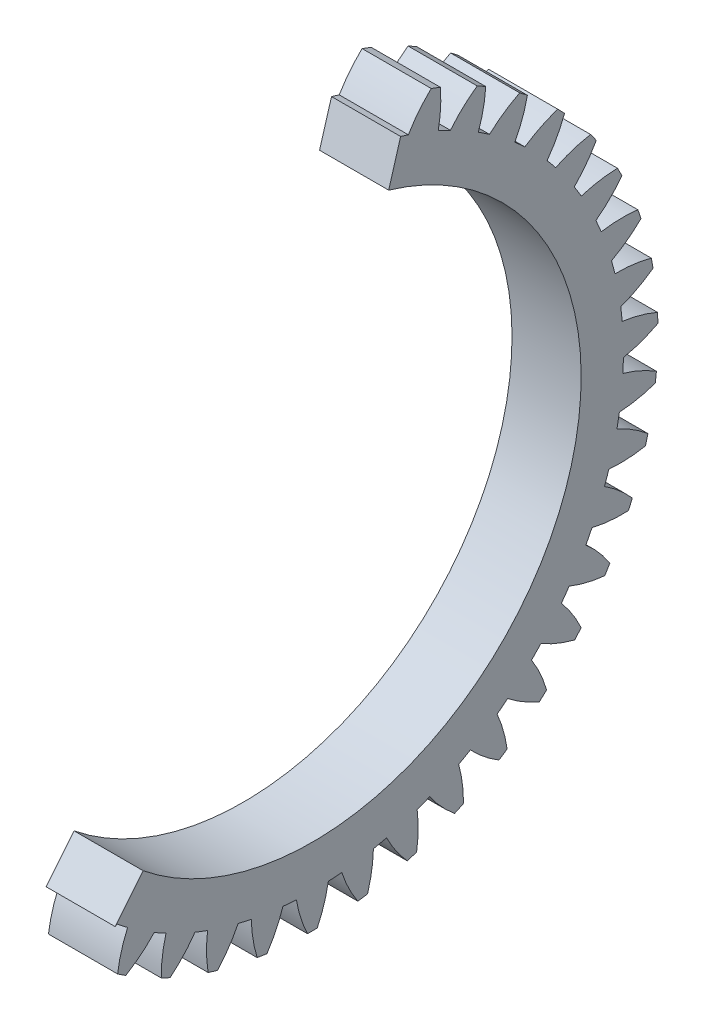
SolidWorks part; units mm, degrees
ref_plane "Plane1" through (0, 0, 0) normal (0, 0, 1) x (1, 0, 0)
ref_plane "Plane2" through (0, 0, 0) normal (0, 1, 0) x (1, 0, 0)
ref_plane "Plane3" through (0, 0, 0) normal (1, 0, 0) x (0, 0, -1)
sketch "HoldingSke" plane through (0, 0, 0) normal (0, 1, 0) x (1, 0, 0)
  line L0 (0, 0) -> (0.3657, -0.341)
  line L1 (-15, 0) -> (100, 0) construction
  line L2 (0, 0) -> (-2.1039, 2.3779)
  line L3 (0, 0) -> (-11.863, 4.5341)
  line L4 (0, 0) -> (6.316, 5.8897)
  line L5 (0, 0) -> (-46.8476, -17.4728)
  line L6 (0, 0) -> (-7.4607, -5.0337)
  line L7 (-2.1039, 2.3779) -> (8.6586, 51.2059)
  line L8 (-76.2, 54.61) -> (-75.2, 54.61)
  line L9 (-71.009, 38.7566) -> (-53.1078, 45.2721)
  line L10 (-76.2, 71.12) -> (104.1128, 71.12)
  line L11 (0, 0) -> (-9, 0)
  line L12 (-76.2, 101.6) -> (-76.133, 101.6)
  line L13 (24.9733, 27.94) -> (52.9518, 28.4284)
  line L14 (24.9733, 27.94) -> (24.9743, 27.94)
  line L15 (24.9733, 27.94) -> (100.4006, 29.5858)
  line L16 (-63.627, -2) -> (-12.827, -2)
  circle A0 centre (0, 0) radius 3
  circle A1 centre (0, 0) radius 37.5
  circle A2 centre (0, 0) radius 37.5
  circle A3 centre (0, 0) radius 3
  dimension "Num_teeth" = 43
  dimension "Pitch_radius" = 180.3128
  dimension "Width" = 9
  dimension "Thickness" = 9
sketch "BasProSke" plane through (0, 0, 0) normal (0, 1, 0) x (1, 0, 0)
  line L0 (-10, 0) -> (60, 0) construction
  line L1 (0, 0) -> (0, 45)
  line L2 (0, 0) -> (9, 0)
  line L3 (9, 0) -> (9, 45)
  line L4 (9, 45) -> (0, 45)
  dimension "Thickness" = 9
  dimension "Diameter" = 90
revolve "Base-Revolve" add sketch "BasProSke" angle 360 about L0
sketch "TooCutSke" plane through (0, 0, 0) normal (1, 0, 0) x (0, 0, -1)
  line L1 (0, 0) -> (0, 107) construction
  line L2 (0, 0) -> (-1.6877, 42.9669) construction
  line L3 (0, 0) -> (-6.274, 85.7216) construction
  line L4 (-1.6877, 42.9669) -> (-3.137, 42.8608) construction
  arc A0 (0.8751, 40.4895) -> (-0.8751, 40.4895) centre (0, 0) ccw
  arc A1 (2.6611, 44.9467) -> (-2.6611, 44.9467) centre (0, 0) ccw
  circle A2 centre (0, 0) radius 43 construction
  circle A3 centre (0, 0) radius 40.4068 construction
  arc A4 (-0.8751, 40.4895) -> (-2.6611, 44.9467) centre (-17.5777, 36.3831) ccw
  arc A5 (2.6611, 44.9467) -> (0.8751, 40.4895) centre (17.5777, 36.3831) ccw
extrude "ToothCut" cut sketch "TooCutSke" along normal through all
fillet "Breaks" [suppressed] radius 0.04 tangent propagation no
fillet "RootFillets" [suppressed] radius 0.501
pattern_circular "TeethCuts" count 43 every 8.372 about axis through (-10, 0, 0) along (1, 0, 0) of "ToothCut", "RootFillets", "Breaks"
sketch "HubNeaOneSke" plane through (0, 0, 0) normal (-1, 0, 0) x (0, 0, 1)
  circle A0 centre (0, 0) radius 37.5
  dimension "Diameter" = 75
extrude "HubNearOne" [suppressed] add sketch "HubNeaOneSke" along normal blind 41.0001
sketch "HubNeaBotSke" plane through (0, 0, 0) normal (-1, 0, 0) x (0, 0, 1)
  circle A0 centre (0, 0) radius 37.5
  dimension "Diameter" = 75
extrude "HubNearBoth" [suppressed] add sketch "HubNeaBotSke" along normal blind 20.5
ref_plane "FarPln" through (9, 0, 0) normal (1, 0, 0) x (0, 0, -1)
sketch "HubFarSke" plane through (9, 0, 0) normal (1, 0, 0) x (0, 0, -1)
  circle A0 centre (0, 0) radius 37.5
  dimension "Diameter" = 75
extrude "HubFar" [suppressed] add sketch "HubFarSke" along normal blind 20.5
sketch "BorSke" plane through (0, 0, 0) normal (1, 0, 0) x (0, 0, -1)
  circle A0 centre (0, 0) radius 3
  dimension "Diameter" = 6
extrude "Bore" cut sketch "BorSke" along normal mid plane 100.0001
sketch "KeySke" plane through (0, 0, 0) normal (1, 0, 0) x (0, 0, -1)
  line L0 (-1, 0) -> (-1, 4)
  line L1 (-1, 4) -> (1, 4)
  line L2 (1, 4) -> (1, 0)
  line L3 (0, 0) -> (0, 34) construction
  line L4 (-1, 0) -> (1, 0)
  dimension "Width" = 2
extrude "Keyway" [suppressed] cut sketch "KeySke" along normal mid plane 100.0001
pattern_circular "Keyway2" [suppressed] count 2 every 90 about axis through (-10, 0, 0) along (1, 0, 0) reverse direction yes
sketch "Szkic1" plane through (0, 0, 0) normal (1, 0, 0) x (0, 0, -1)
  line L1 (0, 0) -> (-31.4677, -38.8559) construction
  line L3 (14.1945, 47.9429) -> (0, 0) construction
  line L4 (-31.4677, -38.8559) -> (-22.0274, -27.1991)
  line L5 (14.1945, 47.9429) -> (9.9361, 33.56)
  line L6 (9.9361, 33.56) -> (14.1945, 47.9429)
  line L7 (-22.0274, -27.1991) -> (-31.4677, -38.8559)
  arc A0 (-31.4677, -38.8559) -> (14.1945, 47.9429) centre (0, 0) cw
  circle A1 centre (0, 0) radius 35 construction
  arc A3 (9.9361, 33.56) -> (-22.0274, -27.1991) centre (0, 0) cw
  arc A5 (-22.0274, -27.1991) -> (9.9361, 33.56) centre (0, 0) ccw
  dimension "D2" = 50
  dimension "D3" = 70
  dimension "D1" = 157.49
sketch "Szkic2" plane through (0, 0, 0) normal (1, 0, 0) x (0, 0, -1)
  line L0 (-31.4677, -38.8559) -> (-22.0274, -27.1991) construction
  line L1 (14.1945, 47.9429) -> (9.9361, 33.56) construction
  line L2 (-31.4677, -38.8559) -> (-22.0274, -27.1991)
  line L3 (14.1945, 47.9429) -> (9.9361, 33.56)
  arc A0 (-22.0274, -27.1991) -> (9.9361, 33.56) centre (0, 0) ccw construction
  arc A1 (14.1945, 47.9429) -> (-31.4677, -38.8559) centre (0, 0) ccw construction
  arc A2 (-22.0274, -27.1991) -> (9.9361, 33.56) centre (0, 0) ccw
  arc A3 (14.1945, 47.9429) -> (-31.4677, -38.8559) centre (0, 0) ccw
extrude "Wytnij-wyciągnięcie1" cut sketch "Szkic2" along normal through all
equation "' \"Module@HoldingSke\" = 6.35"
equation "' \"Num_teeth@HoldingSke\" = 12"
equation "' \"Ap@HoldingSke\" =  20"
equation "' \"Ap@HoldingSke\" = 20"
equation "' \"Width@HoldingSke\" = 0.5 * 25.4"
equation "' \"Hub_dia@HoldingSke\"= 1 * 25.4"
equation "' \"Hub_dia@HoldingSke\" = 1 * 25.4"
equation "' \"Overall_len@HoldingSke\" = 1.0 * 25.4"
equation "' \"Bore@HoldingSke\" = 0.75 * 25.4"
equation "' \"T_dim@HoldingSke\" = 0.1 * 25.4"
equation "' \"Width@KeySke\" = 0.25 * 25.4"
equation "' \"Show_teeth@HoldingSke\" = 13"
equation "' \"Backlash@HoldingSke\" = 0.009 * 25.4"
equation "' \"Addendum_fac@HoldingSke\" = 1.0"
equation "' \"Dedendum_fac@HoldingSke\" = 1.25"
equation "' \"Dedendum_add@HoldingSke\" = 0.00005 * 25.4"
equation "' \"Clearance_fac@HoldingSke\" = 0.25"
equation "\"Pitch@HoldingSke\" = 1 / \"Module@HoldingSke\""
equation "\"Overcut_dia@TooCutSke\" = (\"Num_teeth@HoldingSke\" + 2 * \"Addendum_fac@HoldingSke\") / \"Pitch@HoldingSke\" + 0.002 * 25.4"
equation "\"Pitch_dia@TooCutSke\" = \"Num_teeth@HoldingSke\" / \"Pitch@HoldingSke\""
equation "\"Base_dia@TooCutSke\" = \"Num_teeth@HoldingSke\" / \"Pitch@HoldingSke\" * cos((\"Ap@HoldingSke\"  * 3.14159265 / 180))"
equation "\"Root_dia@TooCutSke\" = (\"Num_teeth@HoldingSke\" + 2) / \"Pitch@HoldingSke\" - 2 * (\"Addendum_fac@HoldingSke\" + \"Dedendum_fac@HoldingSke\") / \"Pitch@HoldingSke\" - \"Dedendum_add@HoldingSke\" * 2"
equation "\"Half_ang@TooCutSke\" = 180 / \"Num_teeth@HoldingSke\""
equation "\"Half_CT@TooCutSke\" = \"Num_teeth@HoldingSke\" / \"Pitch@HoldingSke\" * sin((3.14159265 / 2 / \"Num_teeth@HoldingSke\")) / 2 - 7 * \"Backlash@HoldingSke\" / 4"
equation "\"Flank_rad@TooCutSke\" = \"Num_teeth@HoldingSke\" / \"Pitch@HoldingSke\" / 5"
equation "\"Radius@RootFillets\" = \"Clearance_fac@HoldingSke\" / \"Pitch@HoldingSke\" + \"Dedendum_add@HoldingSke\""
equation "\"Break_rad@Breaks\" = 0.02 / \"Pitch@HoldingSke\""
equation "\"Thickness@HoldingSke\" = \"Width@HoldingSke\""
equation "\"OAL@HoldingSke\" = \"Thickness@HoldingSke\""
equation "\"MHD@HoldingSke\" = (\"Num_teeth@HoldingSke\" + 2) / \"Pitch@HoldingSke\" - 2 * (\"Addendum_fac@HoldingSke\" + \"Dedendum_fac@HoldingSke\")  / \"Pitch@HoldingSke\" - \"Dedendum_add@HoldingSke\" * 2"
equation "\"MBD@HoldingSke\" = (\"Num_teeth@HoldingSke\" + 2) / \"Pitch@HoldingSke\" - 2 * (\"Addendum_fac@HoldingSke\" + \"Dedendum_fac@HoldingSke\")  / \"Pitch@HoldingSke\" - \"Dedendum_add@HoldingSke\" * 2 - 0.002 * 25.4"
equation "\"MHD@HoldingSke\" = ((sgn( \"MHD@HoldingSke\" - \"Hub_dia@HoldingSke\" )-1)*( \"MHD@HoldingSke\" - \"Hub_dia@HoldingSke\" ))/-2+ \"Hub_dia@HoldingSke\""
equation "\"MBD@HoldingSke\" = ((sgn( \"MBD@HoldingSke\" - \"Bore@HoldingSke\" )-1)*( \"MBD@HoldingSke\" - \"Bore@HoldingSke\" ))/-2+ \"Bore@HoldingSke\""
equation "\"OAL@HoldingSke\" = ((sgn( \"OAL@HoldingSke\" - \"Overall_len@HoldingSke\" )+1)*( \"OAL@HoldingSke\" - \"Overall_len@HoldingSke\" ))/2 + \"Overall_len@HoldingSke\" + 0.000002 * 25.4"
equation "\"Num_teeth@TeethCuts\" = int( \"Show_teeth@HoldingSke\" ) + 1"
equation "\"Num_teeth@TeethCuts\" = ((sgn( \"Num_teeth@TeethCuts\" - \"Num_teeth@HoldingSke\" )-1)*( \"Num_teeth@TeethCuts\" - \"Num_teeth@HoldingSke\" ))/-2+ \"Num_teeth@HoldingSke\""
equation "\"Num_teeth@TeethCuts\" = ((sgn( \"Num_teeth@TeethCuts\" - 2.0)+1)*( \"Num_teeth@TeethCuts\" - 2.0))/2 +2.0"
equation "\"Angle@TeethCuts\" = 360.0 / \"Num_teeth@HoldingSke\""
equation "\"Diameter@BasProSke\" = (\"Num_teeth@HoldingSke\" + 2 * \"Addendum_fac@HoldingSke\") / \"Pitch@HoldingSke\""
equation "\"Thickness@BasProSke\"  = \"Thickness@HoldingSke\""
equation "' \"Fillet_rad@BasProSke\" =  \"Thickness@HoldingSke\" * 0.05"
equation "' \"Fillet_rad@BasProSke\" = \"Thickness@HoldingSke\" * 0.05"
equation "\"MHD@HoldingSke\" = ((sgn( \"MHD@HoldingSke\" - \"Root_dia@TooCutSke\" )-1)*( \"MHD@HoldingSke\" - \"Root_dia@TooCutSke\" ))/-2+ \"Root_dia@TooCutSke\""
equation "\"Diameter@HubNeaOneSke\" = \"MHD@HoldingSke\""
equation "\"Length@HubNearOne\" = \"OAL@HoldingSke\" - \"Thickness@BasProSke\""
equation "\"Diameter@HubNeaBotSke\" = \"MHD@HoldingSke\""
equation "\"Length@HubNearBoth\" = ( \"OAL@HoldingSke\" - \"Thickness@BasProSke\" ) / 2.0"
equation "\"Thickness@FarPln\" = \"Thickness@BasProSke\""
equation "\"Diameter@HubFarSke\" = \"MHD@HoldingSke\""
equation "\"Length@HubFar\" = ( \"OAL@HoldingSke\" - \"Thickness@BasProSke\" ) / 2.0"
equation "\"Diameter@BorSke\" = \"MBD@HoldingSke\""
equation "\"D1@Bore\" = \"OAL@HoldingSke\" * 2.0"
equation "\"D1@Keyway\" = \"OAL@HoldingSke\" * 2.0"
equation "\"Offset@KeySke\" = \"T_dim@HoldingSke\" + \"MBD@HoldingSke\" / 2.0"
